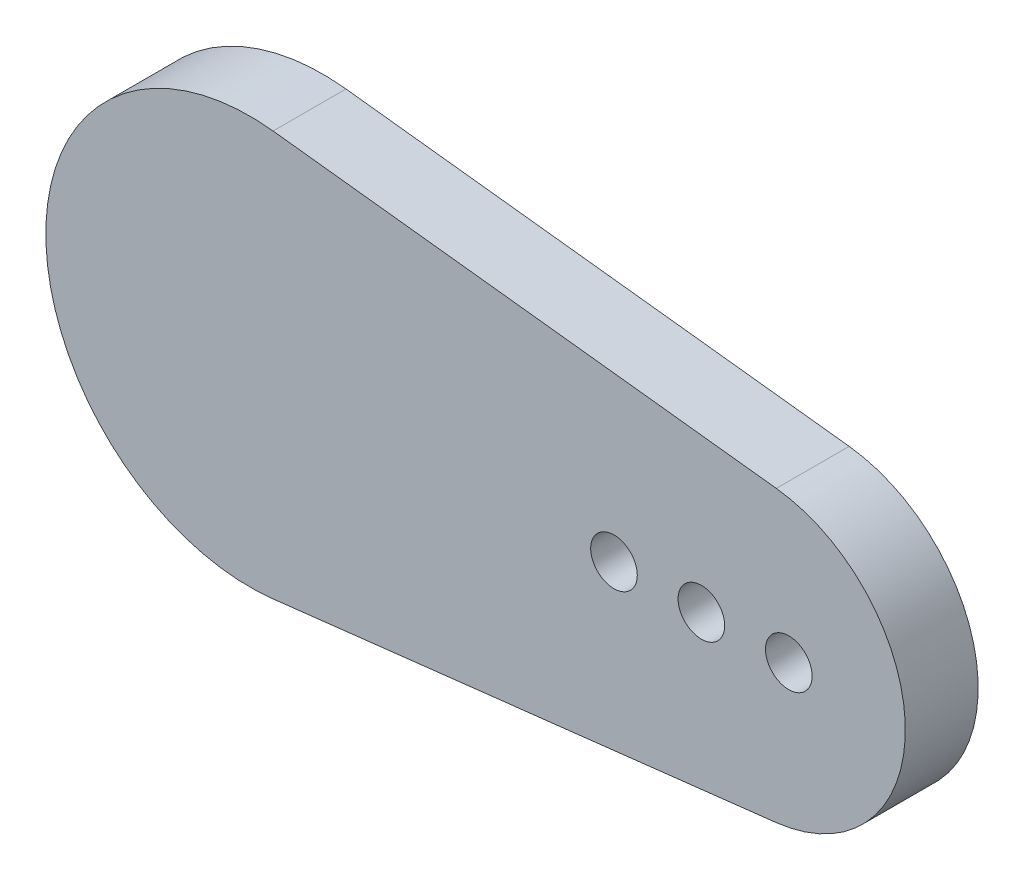
SolidWorks part; units mm, degrees
ref_plane "XY" through (0, 0, 0) normal (0, 0, 1) x (1, 0, 0)
ref_plane "XZ" through (0, 0, 0) normal (0, 1, 0) x (1, 0, 0)
ref_plane "YZ" through (0, 0, 0) normal (1, 0, 0) x (0, 0, -1)
ref_axis "X" through (-88.99, 0, 0) along (1, 0, 0)
ref_axis "Y" through (0, -55, 0) along (0, 1, 0)
ref_axis "Z" through (0, 0, 55) along (0, 0, -1)
sketch "Sketch1" plane through (0, 0, 0) normal (0, 0, 1) x (1, 0, 0)
  line L0 (0.8, -6.9541) -> (18.0714, -4.9672)
  line L1 (18.0714, 4.9672) -> (0.8, 6.9541)
  line L2 (0, 0) -> (17.5, 0) construction
  arc A2 (0.8, 6.9541) -> (0.8, -6.9541) centre (0, 0) ccw
  arc A3 (18.0714, -4.9672) -> (18.0714, 4.9672) centre (17.5, 0) ccw
  circle A4 centre (12.5, 0) radius 0.8
  circle A5 centre (15.5, 0) radius 0.8
  circle A6 centre (18.5, 0) radius 0.8
  point P9 (15.9638, 0)
  dimension "D1" = 7
  dimension "D3" = 5
  dimension "D4" = 1.6
  dimension "D2" = 22.5
  dimension "D5" = 12.5
  dimension "D7" = 3
  dimension "D6" = 3
extrude "Boss-Extrude1" add sketch "Sketch1" along normal blind 2.5
